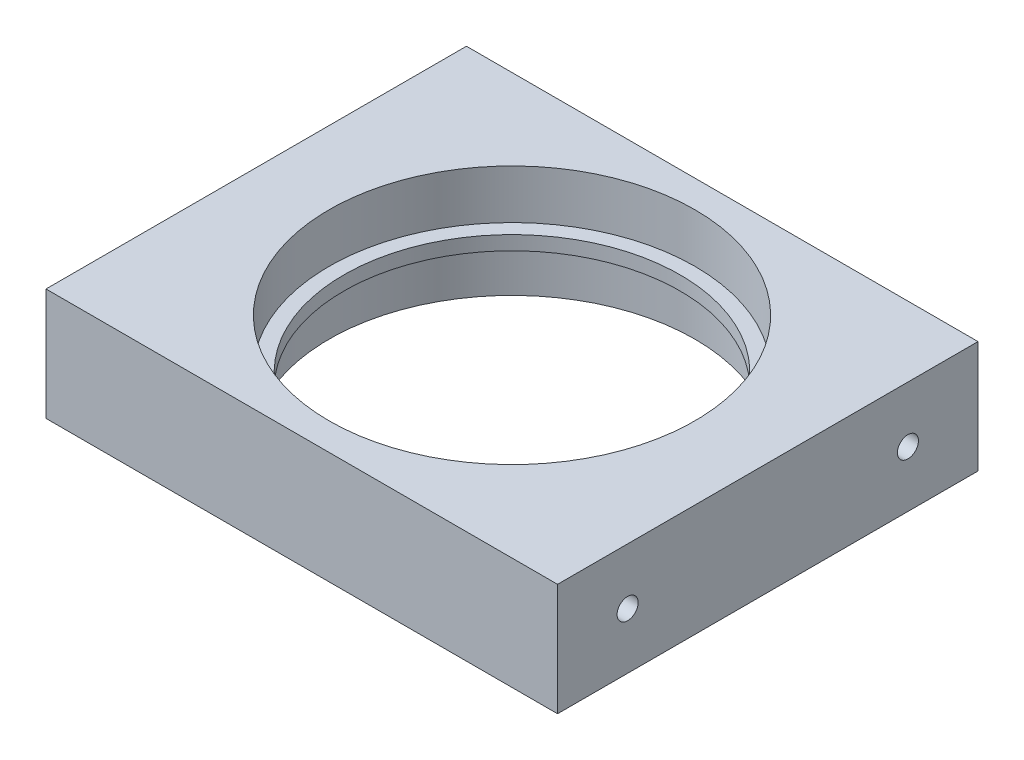
SolidWorks part; units mm, degrees
ref_plane "Front Plane" through (0, 0, 0) normal (0, 0, 1) x (1, 0, 0)
ref_plane "Top Plane" through (0, 0, 0) normal (0, 1, 0) x (1, 0, 0)
ref_plane "Right Plane" through (0, 0, 0) normal (1, 0, 0) x (0, 0, -1)
sketch "Sketch1" plane through (0, 0, 0) normal (0, 1, 0) x (1, 0, 0)
  line L1 (0, 0) -> (73, 0)
  line L2 (0, 0) -> (0, 60)
  line L3 (0, 60) -> (73, 60)
  line L4 (73, 0) -> (73, 60)
  circle A0 centre (36.5, 30) radius 26.1
  point P7 (36.5, 60)
  point P9 (0, 30)
  dimension "D3" = 52.2
  dimension "D1" = 73
  dimension "D2" = 60
extrude "Boss-Extrude1" add sketch "Sketch1" along normal blind 16
sketch "Sketch3" plane through (0, 16, 0) normal (0, 1, 0) x (1, 0, 0)
  circle A0 centre (36.5, 30) radius 24
  circle A1 centre (36.5, 30) radius 26.1 construction
  circle A2 centre (36.5, 30) radius 26.1
  dimension "D1" = 48
extrude "Boss-Extrude2" add sketch "Sketch3" against normal blind 2 from offset 7 offset against normal yes
sketch "Sketch2" plane through (73, 0, 0) normal (1, 0, 0) x (0, 0, -1)
  line L0 (0, 16) -> (0, 0) construction
  line L1 (60, 16) -> (60, 0) construction
  circle A0 centre (10, 8) radius 1.5
  circle A1 centre (50, 8) radius 1.5
  point P6 (0, 8)
  dimension "D3" = 3
  dimension "D1" = 10
  dimension "D2" = 10
extrude "Cut-Extrude1" cut sketch "Sketch2" against normal blind 15
extrude "Cut-Extrude2" cut sketch "Sketch2<2>" along normal blind 15 from surface starting at face at (0, 8, -30)
sketch "Sketch2<2>" plane through (73, 0, 0) normal (1, 0, 0) x (0, 0, -1) same geometry as "Sketch2"
